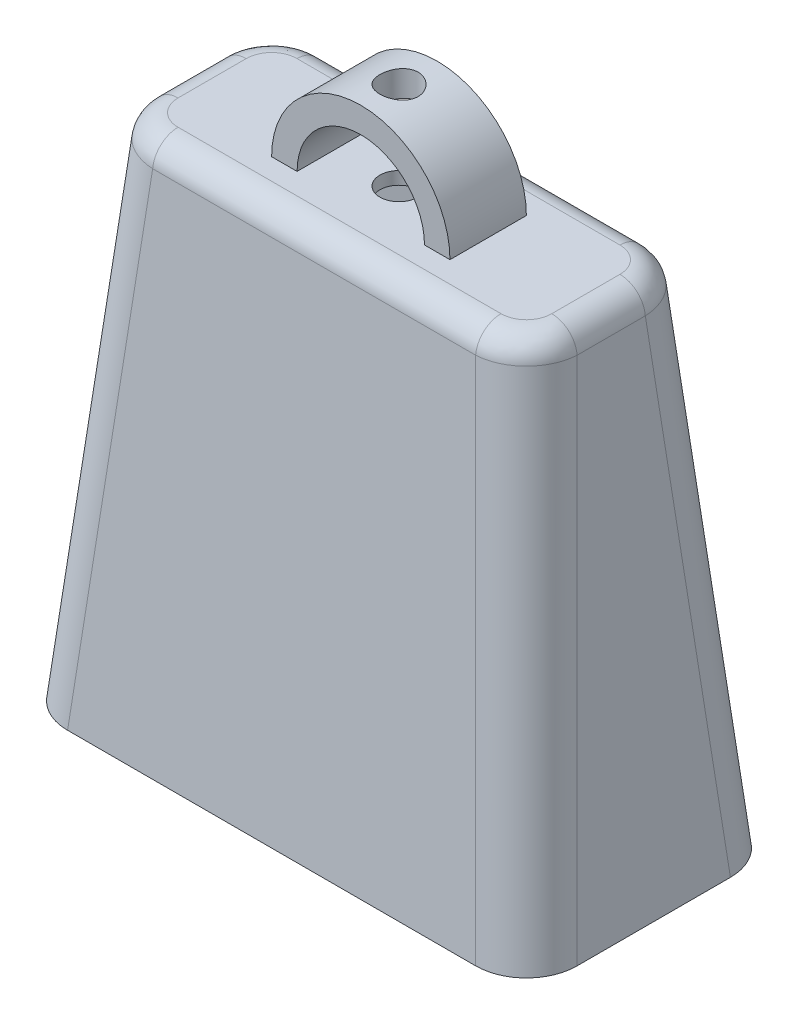
SolidWorks part; units mm, degrees
ref_plane "Front Plane" through (0, 0, 0) normal (0, 0, 1) x (1, 0, 0)
ref_plane "Top Plane" through (0, 0, 0) normal (0, 1, 0) x (1, 0, 0)
ref_plane "Right Plane" through (0, 0, 0) normal (1, 0, 0) x (0, 0, -1)
sketch "Sketch1" plane through (0, 0, 0) normal (0, 1, 0) x (1, 0, 0)
  line L1 (-50, -25) -> (50, -25)
  line L2 (-50, -25) -> (-50, 25)
  line L3 (-50, 25) -> (50, 25)
  line L4 (50, -25) -> (50, 25)
  line L5 (-50, -25) -> (50, 25) construction
  line L6 (-50, 25) -> (50, -25) construction
  point P0 (0, 0)
  dimension "D1" = 100
  dimension "D2" = 50
extrude "Boss-Extrude1" add sketch "Sketch1" along normal blind 100 draft 5 contours L2 L3 L4 L1
fillet "Fillet1" radius 10 4 edges at (-45.6256, 50, -20.6256) (45.6256, 50, -20.6256) (-45.6256, 50, 20.6256) (45.6256, 50, 20.6256)
fillet "Fillet2" radius 5 8 edges at (38.3379, 100, -13.3379) (41.2511, 100, 0) (38.3379, 100, 13.3379) (0, 100, 16.2511) (-38.3379, 100, 13.3379) (-41.2511, 100, 0) (-38.3379, 100, -13.3379) (0, 100, -16.2511)
shell "Shell1" thickness 2.5 removed face at (0, 0, 0)
sketch "Sketch2" plane through (0, 100, 0) normal (0, 1, 0) x (1, 0, 0)
  line L0 (0, 0) -> (0, -11.6695) construction
  line L1 (-31.6885, -11.6695) -> (31.6885, -11.6695) construction
  line L3 (-17.5, -7.5) -> (-12.5, -7.5)
  line L4 (-17.5, -7.5) -> (-17.5, 7.5)
  line L5 (-17.5, 7.5) -> (-12.5, 7.5)
  line L6 (-12.5, -7.5) -> (-12.5, 7.5)
  line L7 (-17.5, -7.5) -> (-12.5, 7.5) construction
  line L8 (-17.5, 7.5) -> (-12.5, -7.5) construction
  point P5 (-15, 0)
  point P10 (0, 0)
  dimension "D1" = 15
  dimension "D2" = 5
  dimension "D3" = 15
revolve "Revolve1" add sketch "Sketch2" angle 180 about L0
sketch "Sketch4" plane through (0, 0, 0) normal (0, 1, 0) x (1, 0, 0)
  circle A0 centre (0, 0) radius 3.75
  dimension "D1" = 7.5
extrude "Cut-Extrude1" cut sketch "Sketch4" along normal through all
